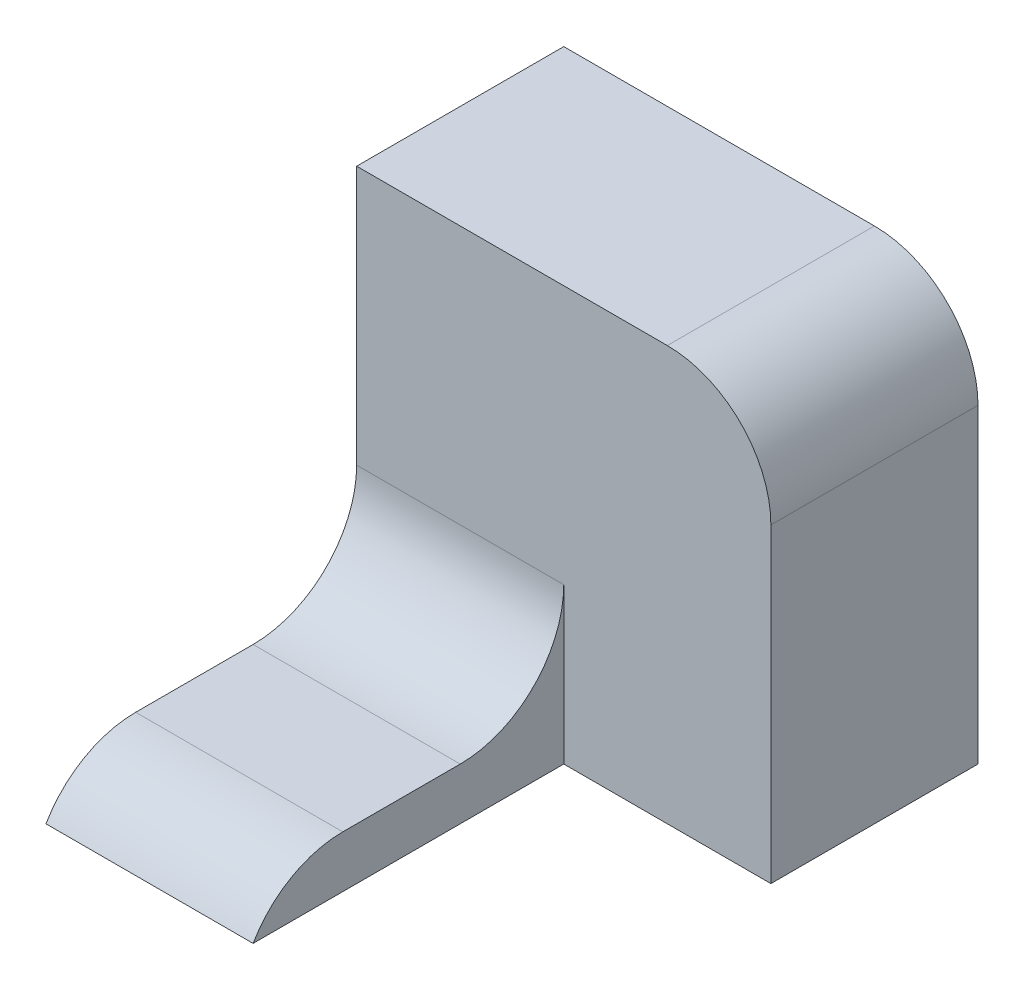
SolidWorks part; units mm, degrees
ref_plane "Front Plane" through (0, 0, 0) normal (0, 0, 1) x (1, 0, 0)
ref_plane "Top Plane" through (0, 0, 0) normal (0, 1, 0) x (1, 0, 0)
ref_plane "Right Plane" through (0, 0, 0) normal (1, 0, 0) x (0, 0, -1)
sketch "Sketch1" plane through (0, 0, 0) normal (0, 0, 1) x (1, 0, 0)
  line L1 (-30, -5) -> (-10, -5)
  line L2 (-10, -5) -> (-10, 0)
  line L3 (-10, 0) -> (-30, 0)
  line L4 (-30, 0) -> (-30, -5)
  dimension "D1" = 20
  dimension "Width" = 5
extrude "Boss-Extrude1" add sketch "Sketch1" along normal blind 30
sketch "Sketch2" plane through (0, 0, 0) normal (0, 0, 1) x (1, 0, 0)
  line L1 (-30, -5) -> (10, -5)
  line L2 (10, -5) -> (10, 35)
  line L3 (10, 35) -> (-30, 35)
  line L4 (-30, 35) -> (-30, -5)
  dimension "D1" = 40
  dimension "Width" = 40
extrude "Boss-Extrude2" add sketch "Sketch2" against normal blind 20
fillet "Fillet1" radius 10 3 edges at (-20, 0, 0) (10, 35, -10) (-20, 0, 30)
